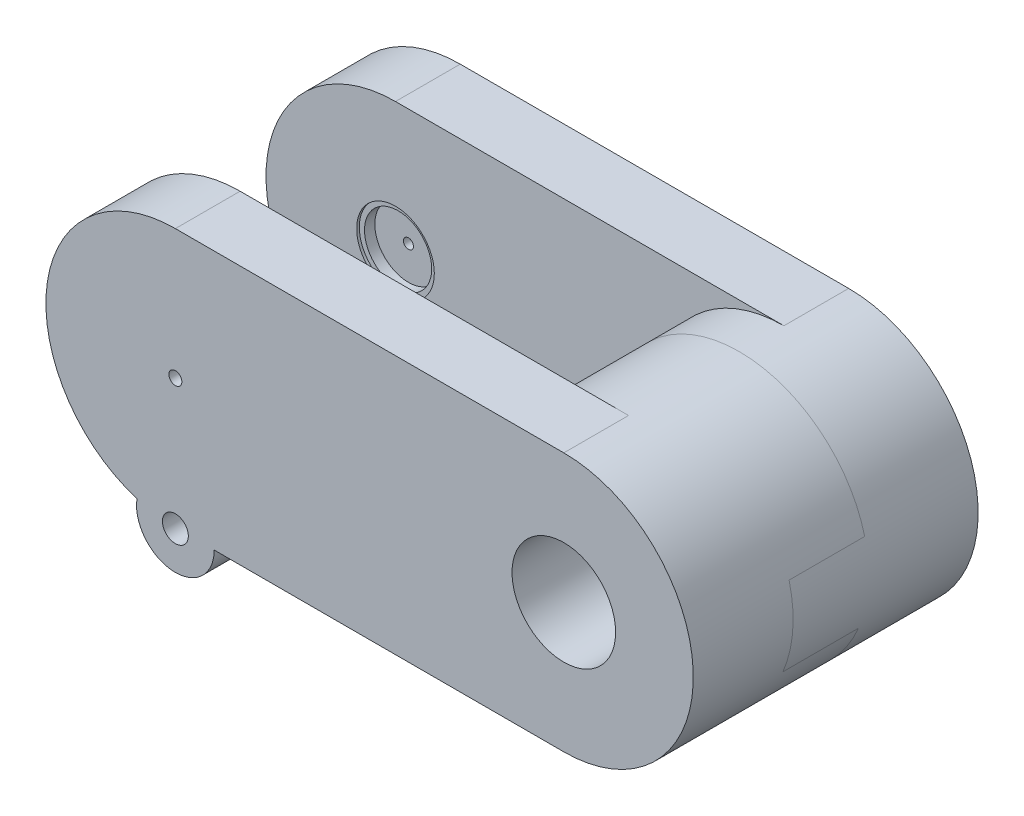
SolidWorks part; units mm, degrees
material "Plain Carbon Steel"
ref_plane "Front Plane" through (0, 0, 0) normal (0, 0, 1) x (1, 0, 0)
ref_plane "Top Plane" through (0, 0, 0) normal (0, 1, 0) x (1, 0, 0)
ref_plane "Right Plane" through (0, 0, 0) normal (1, 0, 0) x (0, 0, -1)
sketch "Sketch1" plane through (0, 0, 0) normal (0, 0, 1) x (1, 0, 0)
  line L1 (0, 50) -> (150, 50)
  line L2 (0, 50) -> (0, -50)
  line L3 (0, -50) -> (150, -50)
  line L4 (150, 50) -> (150, -50)
  circle A0 centre (0, 0) radius 50
  circle A2 centre (150, 0) radius 50
extrude "Boss-Extrude1" add sketch "Sketch1" along normal blind 25 contours L2 A0 | L2 A0 | A2 L1 A0 L3 | L4 A2 | L4 A2 region at (21.2207, 0, 0) region at (75, 0, 0) region at (-21.2207, 0, 0) region at (171.2207, 0, 0) region at (128.7793, 0, 0)
sketch "Sketch2" plane through (0, 0, 25) normal (0, 0, 1) x (1, 0, 0)
  line L0 (150, 50) -> (150, -50)
  circle A0 centre (0, 0) radius 2.5
  arc A3 (150, -50) -> (150, 50) centre (150, 0) ccw construction
  circle A4 centre (150, 0) radius 20
extrude "Cut-Extrude1" cut sketch "Sketch2" against normal through all contours L0 A4 | L0 A4 | A0 region at (158.4883, 0, 25) region at (141.5117, 0, 25)
sketch "Sketch3" plane through (0, 0, 0) normal (0, 0, -1) x (-1, 0, 0)
  circle A0 centre (-150, 0) radius 50
extrude "Boss-Extrude2" add sketch "Sketch3" along normal blind 60
sketch "Sketch4" plane through (0, 0, -60) normal (0, 0, -1) x (-1, 0, 0)
  line L1 (-150, -50) -> (0, -50)
  line L2 (-150, -50) -> (-150, 50)
  line L3 (-150, 50) -> (0, 50)
  line L4 (0, -50) -> (0, 50)
  circle A0 centre (-150, 0) radius 50
  circle A1 centre (0, 0) radius 50
  circle M6 centre (-150, 0) radius 50
extrude "Boss-Extrude3" add sketch "Sketch4" along normal blind 25 contours L2 M6 | L2 M6 | A1 L3 L1 M6 | L4 A1 | L4 A1 region at (75, 0, -60) region at (171.2207, 0, -60) region at (128.7793, 0, -60) region at (21.2207, 0, -60) region at (-21.2207, 0, -60)
sketch "Sketch5" plane through (0, 0, -85) normal (0, 0, -1) x (-1, 0, 0)
  circle A0 centre (0, 0) radius 1.935
  circle A2 centre (-150, 0) radius 20
extrude "Cut-Extrude2" cut sketch "Sketch5" against normal through all
sketch "Sketch6" plane through (0, 0, -60) normal (0, 0, 1) x (1, 0, 0)
  circle A0 centre (0, 0) radius 14.99
extrude "Cut-Extrude3" cut sketch "Sketch6" against normal blind 1.01
sketch "Sketch7" plane through (0, 0, -61.01) normal (0, 0, 1) x (1, 0, 0)
  circle A0 centre (0, 0) radius 12.98
extrude "Cut-Extrude4" cut sketch "Sketch7" against normal blind 3.98
ref_plane "Plane1" through (0, -50, 0) normal (0, 0, -1) x (-1, 0, 0)
sketch "Sketch9" plane through (0, 0, 0) normal (0, 0, -1) x (-1, 0, 0)
  line L1 (-9, 8.1) -> (9, 8.1)
  line L2 (-9, 8.1) -> (-9, -8.1)
  line L3 (-9, -8.1) -> (9, -8.1)
  line L4 (9, 8.1) -> (9, -8.1)
  dimension "D1" = 18
  dimension "D2" = 16.2
extrude "Cut-Extrude5" cut sketch "Sketch9" against normal blind 11.23
sketch "Sketch10" plane through (9, 0, 0) normal (-1, 0, 0) x (0, 0, 1)
  line L0 (11.23, -8.1) -> (0, -8.1) construction
  line L1 (2.9617, -8.1) -> (16.8051, -8.1)
  line L2 (2.9617, -8.1) -> (2.9617, 7.9462)
  line L3 (2.9617, 7.9462) -> (16.8051, 7.9462)
  line L4 (16.8051, -8.1) -> (16.8051, 7.9462)
extrude "Cut-Extrude6" cut sketch "Sketch10" against normal blind 90
sketch "Sketch11" plane through (0, 0, 0) normal (0, 0, -1) x (-1, 0, 0)
  line L0 (-9, -8.1) -> (9, -8.1) construction
  line L1 (-9, 8.1) -> (-98.2243, 8.1)
  line L2 (-9, 8.1) -> (-9, -8.1)
  line L3 (-9, -8.1) -> (-98.2243, -8.1)
  line L4 (-98.2243, 8.1) -> (-98.2243, -8.1)
extrude "Cut-Extrude7" cut sketch "Sketch11" against normal blind 10
sketch "Sketch12" plane through (0, 0, 0) normal (0, 0, -1) x (-1, 0, 0)
  line L0 (0, -50) -> (-150, -50) construction
  line L1 (-98.2243, -8.1) -> (9, -8.1) construction
  line L2 (-99.6388, -50) -> (-119.7639, -50)
  line L3 (-81.1967, -8.1) -> (-98.2243, -8.1)
  spline S0 degree 2 poles (-98.2243, -8.1) (-98.7811, -33.7918) (-119.7639, -50) knots 0 0 0 1 1 1
  spline S1 degree 2 poles (-81.1967, -8.1) (-78.5998, -33.6222) (-99.6388, -50) knots 0 0 0 1 1 1
extrude "Cut-Extrude8" cut sketch "Sketch12" against normal blind 15
sketch "Sketch14" plane through (0, 0, 25) normal (0, 0, 1) x (1, 0, 0)
  line L0 (0, -50) -> (150, -50) construction
  line L1 (15, -50) -> (-14.8303, -47.75)
  arc A0 (15, -50) -> (-14.8303, -47.75) centre (0, -50) cw
  arc A1 (0, 50) -> (0, -50) centre (0, 0) ccw construction
extrude "Boss-Extrude4" add sketch "Sketch14" against normal through all
sketch "Sketch15" plane through (0, 0, -85) normal (0, 0, -1) x (-1, 0, 0)
  circle A0 centre (0, -50.3568) radius 5
extrude "Cut-Extrude9" cut sketch "Sketch15" against normal through all
sketch "Sketch16" plane through (-3.6651, -48.5921, 0) normal (0.0752, 0.9972, 0) x (0.9972, -0.0752, 0)
  line L1 (-18.6749, 0) -> (18.7182, 0)
  line L2 (-18.6749, 0) -> (-18.6749, 60)
  line L3 (-18.6749, 60) -> (18.7182, 60)
  line L4 (18.7182, 0) -> (18.7182, 60)
extrude "Cut-Extrude11" cut sketch "Sketch16" against normal blind 20
sketch "Sketch17" plane through (18.6651, -1.4079, 0) normal (-0.9972, 0.0752, 0) x (0, 0, 1)
  line L0 (-60, -50.9866) -> (0, -50.9866) construction
  line L1 (0, -50.9866) -> (-59.8133, -50.9866)
  line L2 (0, -50.9866) -> (0, -48.6413)
  line L3 (0, -48.6413) -> (-59.8133, -48.6413)
  line L4 (-59.8133, -50.9866) -> (-59.8133, -48.6413)
extrude "Cut-Extrude12" cut sketch "Sketch17" against normal blind 20
sketch "Sketch18" plane through (0, 0, 0) normal (1, 0, 0) x (0, 0, -1)
  line L0 (42.7478, 55.9773) -> (42.7478, 12.3882)
  line L1 (42.7478, 12.3882) -> (13.5513, 12.3882)
  line L2 (13.5513, 12.3882) -> (13.5513, -19.4812)
  line L3 (13.5513, -19.4812) -> (42.7478, -19.4812)
  line L4 (42.7478, -19.4812) -> (42.7478, -74.9957)
split "Split1" trim tools "Sketch18" bodies to split 116 resulting bodies 117 118
